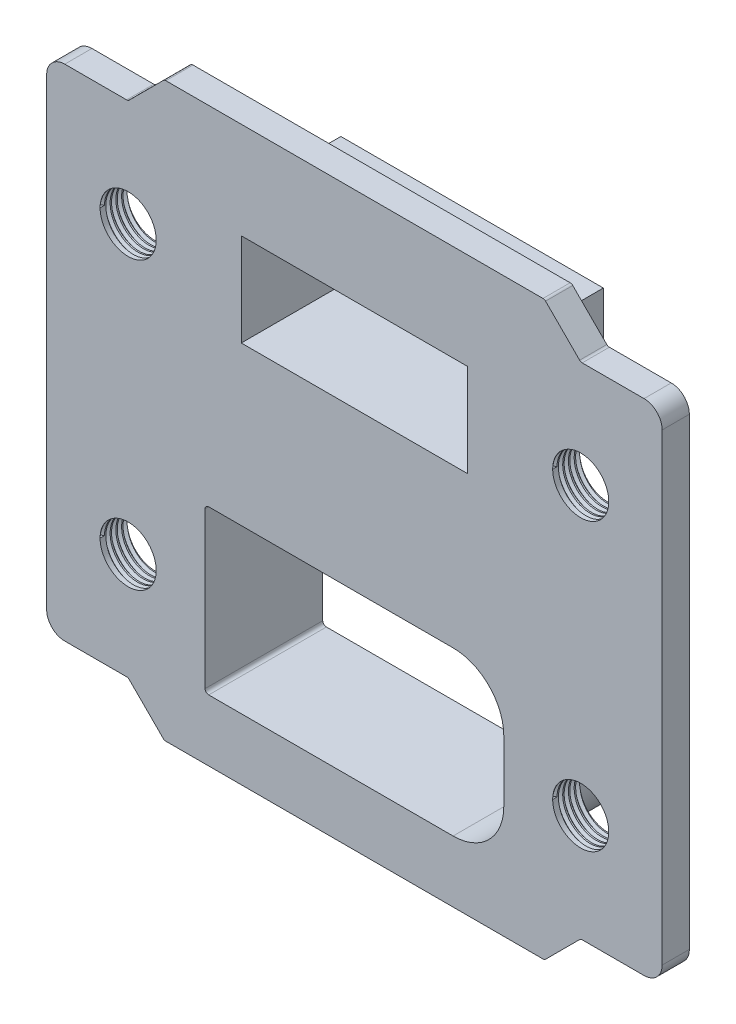
SolidWorks part; units mm, degrees
ref_plane "Спереди" through (0, 0, 0) normal (0, 0, 1) x (1, 0, 0)
ref_plane "Сверху" through (0, 0, 0) normal (0, 1, 0) x (1, 0, 0)
ref_plane "Справа" through (0, 0, 0) normal (1, 0, 0) x (0, 0, -1)
sketch "Эскиз1" plane through (0, 0, 0) normal (0, 0, 1) x (1, 0, 0)
  line L0 (-17, -4.9) -> (-17, 4.9)
  line L1 (-16, 5.9) -> (-12.5828, 5.9)
  line L2 (-12.4414, 5.9586) -> (-10.5586, 7.8414)
  line L3 (-10.4172, 7.9) -> (10.4172, 7.9)
  line L4 (10.5586, 7.8414) -> (12.4414, 5.9586)
  line L5 (12.5828, 5.9) -> (16, 5.9)
  line L6 (17, 4.9) -> (17, -4.9)
  line L7 (17, -4.9) -> (17, -10.9)
  line L8 (-17, -4.9) -> (-17, -10.9)
  line L10 (-6.25, 2.565) -> (6.25, 2.565)
  line L11 (-6.25, 2.565) -> (-6.25, -2.565)
  line L12 (-17, 0) -> (17, 0) construction
  line L13 (-6.25, -2.565) -> (6.25, -2.565)
  line L14 (6.25, 2.565) -> (6.25, -2.565)
  line L15 (-6.25, 2.565) -> (6.25, -2.565) construction
  line L16 (-6.25, -2.565) -> (6.25, 2.565) construction
  line L21 (-8.25, -20.3) -> (8.25, -11.3) construction
  line L22 (-8.25, -11.3) -> (8.25, -20.3) construction
  line L23 (-17, -15.8) -> (17, -15.8) construction
  line L24 (8.25, -14.1) -> (8.25, -17.5)
  line L25 (-8.05, -20.3) -> (5.45, -20.3)
  line L26 (-8.25, -11.5) -> (-8.25, -20.1)
  line L27 (-8.05, -11.3) -> (5.45, -11.3)
  line L30 (17, -20.7) -> (17, -10.9)
  line L31 (12.5828, -21.7) -> (16, -21.7)
  line L32 (10.5586, -23.6414) -> (12.4414, -21.7586)
  line L33 (-10.4172, -23.7) -> (10.4172, -23.7)
  line L34 (-12.4414, -21.7586) -> (-10.5586, -23.6414)
  line L35 (-16, -21.7) -> (-12.5828, -21.7)
  line L36 (-17, -10.9) -> (-17, -20.7)
  circle A0 centre (-12.5, 0) radius 1.55
  circle A1 centre (12.5, 0) radius 1.55
  arc A2 (16, 5.9) -> (17, 4.9) centre (16, 4.9) cw
  arc A5 (-17, 4.9) -> (-16, 5.9) centre (-16, 4.9) cw
  arc A12 (-12.5828, 5.9) -> (-12.4414, 5.9586) centre (-12.5828, 6.1) ccw
  arc A13 (-10.5586, 7.8414) -> (-10.4172, 7.9) centre (-10.4172, 7.7) cw
  arc A14 (12.4414, 5.9586) -> (12.5828, 5.9) centre (12.5828, 6.1) ccw
  arc A15 (10.4172, 7.9) -> (10.5586, 7.8414) centre (10.4172, 7.7) cw
  arc A20 (-8.25, -20.1) -> (-8.05, -20.3) centre (-8.05, -20.1) ccw
  arc A21 (-8.05, -11.3) -> (-8.25, -11.5) centre (-8.05, -11.5) ccw
  arc A22 (10.4172, -23.7) -> (10.5586, -23.6414) centre (10.4172, -23.5) ccw
  arc A23 (12.4414, -21.7586) -> (12.5828, -21.7) centre (12.5828, -21.9) cw
  arc A24 (-10.5586, -23.6414) -> (-10.4172, -23.7) centre (-10.4172, -23.5) ccw
  arc A25 (-12.5828, -21.7) -> (-12.4414, -21.7586) centre (-12.5828, -21.9) cw
  arc A28 (5.45, -20.3) -> (8.25, -17.5) centre (5.45, -17.5) ccw
  arc A29 (5.45, -11.3) -> (8.25, -14.1) centre (5.45, -14.1) cw
  arc A30 (-17, -20.7) -> (-16, -21.7) centre (-16, -20.7) ccw
  arc A33 (16, -21.7) -> (17, -20.7) centre (16, -20.7) ccw
  circle A34 centre (12.5, -15.8) radius 1.55
  circle A35 centre (-12.5, -15.8) radius 1.55
  point P0 (0, 0)
  point P25 (-17, -5.9)
  point P28 (-17, 5.9)
  point P51 (-12.5, 5.9)
  point P56 (12.5, 5.9)
  point P121 (12.5, -21.7)
  point P122 (-12.5, -21.7)
  point P124 (0, -15.8)
  point P125 (-17, -21.7)
  point P126 (-17, -9.9)
  dimension "D4" = 3.1
  dimension "D7" = 1
  dimension "D11" = 2.8
  dimension "D14" = 2.8
  dimension "D17" = 0.2
  dimension "D21" = 3.1
  dimension "D22" = 3.1
  dimension "D1" = 34
  dimension "D2" = 11.8
  dimension "D5" = 25
  dimension "D6" = 12.5
  dimension "D3" = 13.5
  dimension "D13" = 13.5
  dimension "D15" = 3.4
  dimension "D16" = 8.6
  dimension "D18" = 3.4
  dimension "D19" = 8.75
  dimension "D20" = 6.2
  dimension "D23" = 4.5
  dimension "D24" = 5.9
  dimension "D25" = 5.9
  dimension "D26" = 4.5
  dimension "D27" = 23.7
  dimension "D28" = 9.8
  dimension "D8" = 5.13
  dimension "D9" = 12.5
extrude "Бобышка-Вытянуть1" add sketch "Эскиз1" against normal blind 1.5
sketch "Sketch1" plane through (0, 0, -1.5) normal (0, 0, -1) x (-1, 0, 0)
  line L7 (6.25, 2.565) -> (6.25, -2.565) construction
  line L8 (6.25, -2.565) -> (-6.25, -2.565) construction
  line L9 (-6.25, -2.565) -> (-6.25, 2.565) construction
  line L10 (-6.25, 2.565) -> (6.25, 2.565) construction
  line L11 (7.25, -3.565) -> (7.25, 3.565)
  line L12 (-7.25, -3.565) -> (7.25, -3.565)
  line L13 (-7.25, 3.565) -> (-7.25, -3.565)
  line L14 (7.25, 3.565) -> (-7.25, 3.565)
  line L15 (7.25, -3.565) -> (7.25, 3.565)
  line L16 (-7.25, -3.565) -> (7.25, -3.565)
  line L17 (-7.25, 3.565) -> (-7.25, -3.565)
  line L18 (7.25, 3.565) -> (-7.25, 3.565)
  line L19 (6.25, 2.565) -> (6.25, -2.565)
  line L20 (6.25, -2.565) -> (-6.25, -2.565)
  line L21 (-6.25, -2.565) -> (-6.25, 2.565)
  line L22 (-6.25, 2.565) -> (6.25, 2.565)
  line L23 (8.25, -11.5) -> (8.25, -20.1) construction
  line L24 (8.05, -20.3) -> (-5.45, -20.3) construction
  line L25 (-8.25, -17.5) -> (-8.25, -14.1) construction
  line L26 (-5.45, -11.3) -> (8.05, -11.3) construction
  line L27 (9.25, -20.1) -> (9.25, -11.5)
  line L28 (-5.45, -21.3) -> (8.05, -21.3)
  line L29 (-9.25, -14.1) -> (-9.25, -17.5)
  line L30 (8.05, -10.3) -> (-5.45, -10.3)
  line L31 (9.25, -20.1) -> (9.25, -11.5)
  line L32 (-5.45, -21.3) -> (8.05, -21.3)
  line L33 (-9.25, -14.1) -> (-9.25, -17.5)
  line L34 (8.05, -10.3) -> (-5.45, -10.3)
  line L35 (8.25, -11.5) -> (8.25, -20.1)
  line L36 (8.05, -20.3) -> (-5.45, -20.3)
  line L37 (-8.25, -17.5) -> (-8.25, -14.1)
  line L38 (-5.45, -11.3) -> (8.05, -11.3)
  arc A20 (8.05, -20.3) -> (8.25, -20.1) centre (8.05, -20.1) ccw construction
  arc A21 (8.25, -11.5) -> (8.05, -11.3) centre (8.05, -11.5) ccw construction
  arc A22 (-8.25, -17.5) -> (-5.45, -20.3) centre (-5.45, -17.5) ccw construction
  arc A23 (-5.45, -11.3) -> (-8.25, -14.1) centre (-5.45, -14.1) ccw construction
  arc A24 (9.25, -11.5) -> (8.05, -10.3) centre (8.05, -11.5) ccw
  arc A25 (8.05, -21.3) -> (9.25, -20.1) centre (8.05, -20.1) ccw
  arc A26 (-9.25, -17.5) -> (-5.45, -21.3) centre (-5.45, -17.5) ccw
  arc A27 (-5.45, -10.3) -> (-9.25, -14.1) centre (-5.45, -14.1) ccw
  arc A28 (9.25, -11.5) -> (8.05, -10.3) centre (8.05, -11.5) ccw
  arc A29 (8.05, -21.3) -> (9.25, -20.1) centre (8.05, -20.1) ccw
  arc A30 (-9.25, -17.5) -> (-5.45, -21.3) centre (-5.45, -17.5) ccw
  arc A31 (-5.45, -10.3) -> (-9.25, -14.1) centre (-5.45, -14.1) ccw
  arc A32 (8.05, -20.3) -> (8.25, -20.1) centre (8.05, -20.1) ccw
  arc A33 (8.25, -11.5) -> (8.05, -11.3) centre (8.05, -11.5) ccw
  arc A34 (-8.25, -17.5) -> (-5.45, -20.3) centre (-5.45, -17.5) ccw
  arc A35 (-5.45, -11.3) -> (-8.25, -14.1) centre (-5.45, -14.1) ccw
  dimension "D1" = 1
  dimension "D2" = 1
extrude "Boss-Extrude1" add sketch "Sketch1" along normal blind 5
thread "Thread1" pitch 0.3175 method cut profile "Thread Profile1" start angle 0, offset 0, length 0, pitch 0.3175, diameter 3.1
ref_plane "Plane1" through (-14.05, -15.8, 0) normal (0, -1, 0) x (-1, 0, 0)
sketch "Thread Profile1" plane through (-14.05, -15.8, 0) normal (0, -1, 0) x (-1, 0, 0)
  line L0 (0, 0) -> (0, 0.3175) construction
  line L1 (0, 0) -> (0.1719, 0.0992)
  line L2 (0.1719, 0.0992) -> (0.1719, 0.1389)
  line L3 (0.1719, 0.1389) -> (0, 0.2381)
  line L4 (0.1719, 0.1191) -> (0, 0.1191) construction
  line L11 (0, 0) -> (0, 0.2381)
  point P2 (0, 0)
  dimension "Pitch" = 0.3175
  dimension "Profile_Angle" = 60
  dimension "Profile_Land" = 0.0397
  dimension "Profile_Height" = 0.1719
thread "Thread2" pitch 0.3175 method cut profile "Thread Profile2" start angle 0, offset 0, length 0, pitch 0.3175, diameter 3.1
ref_plane "Plane2" through (10.95, -15.8, 0) normal (0, -1, 0) x (-1, 0, 0)
sketch "Thread Profile2" plane through (10.95, -15.8, 0) normal (0, -1, 0) x (-1, 0, 0)
  line L0 (0, 0) -> (0, 0.3175) construction
  line L1 (0, 0) -> (0.1719, 0.0992)
  line L2 (0.1719, 0.0992) -> (0.1719, 0.1389)
  line L3 (0.1719, 0.1389) -> (0, 0.2381)
  line L4 (0.1719, 0.1191) -> (0, 0.1191) construction
  line L11 (0, 0) -> (0, 0.2381)
  point P2 (0, 0)
  dimension "Pitch" = 0.3175
  dimension "Profile_Angle" = 60
  dimension "Profile_Land" = 0.0397
  dimension "Profile_Height" = 0.1719
thread "Thread5" pitch 0.3175 method cut profile "Thread Profile5" start angle 0, offset 0, length 0, pitch 0.3175, diameter 3.1
ref_plane "Plane5" through (-14.05, 0, 0) normal (0, -1, 0) x (-1, 0, 0)
sketch "Thread Profile5" plane through (-14.05, 0, 0) normal (0, -1, 0) x (-1, 0, 0)
  line L0 (0, 0) -> (0, 0.3175) construction
  line L1 (0, 0) -> (0.1719, 0.0992)
  line L2 (0.1719, 0.0992) -> (0.1719, 0.1389)
  line L3 (0.1719, 0.1389) -> (0, 0.2381)
  line L4 (0.1719, 0.1191) -> (0, 0.1191) construction
  line L11 (0, 0) -> (0, 0.2381)
  point P2 (0, 0)
  dimension "Pitch" = 0.3175
  dimension "Profile_Angle" = 60
  dimension "Profile_Land" = 0.0397
  dimension "Profile_Height" = 0.1719
thread "Thread6" pitch 0.3175 method cut profile "Thread Profile6" start angle 0, offset 0, length 0, pitch 0.3175, diameter 3.1
ref_plane "Plane6" through (10.95, 0, 0) normal (0, -1, 0) x (-1, 0, 0)
sketch "Thread Profile6" plane through (10.95, 0, 0) normal (0, -1, 0) x (-1, 0, 0)
  line L0 (0, 0) -> (0, 0.3175) construction
  line L1 (0, 0) -> (0.1719, 0.0992)
  line L2 (0.1719, 0.0992) -> (0.1719, 0.1389)
  line L3 (0.1719, 0.1389) -> (0, 0.2381)
  line L4 (0.1719, 0.1191) -> (0, 0.1191) construction
  line L11 (0, 0) -> (0, 0.2381)
  point P2 (0, 0)
  dimension "Pitch" = 0.3175
  dimension "Profile_Angle" = 60
  dimension "Profile_Land" = 0.0397
  dimension "Profile_Height" = 0.1719
equation "\"D6@Эскиз1\"=\"D5@Эскиз1\"/2"
